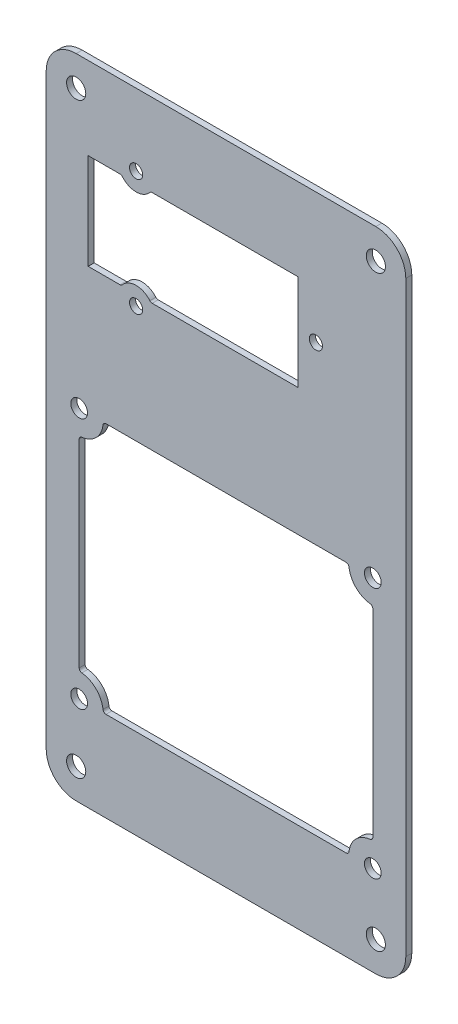
SolidWorks part; units mm, degrees
ref_plane "正面" through (0, 0, 0) normal (0, 0, 1) x (1, 0, 0)
ref_plane "平面" through (0, 0, 0) normal (0, 1, 0) x (1, 0, 0)
ref_plane "右側面" through (0, 0, 0) normal (1, 0, 0) x (0, 0, -1)
sketch "ｽｹｯﾁ1" plane through (0, 0, 0) normal (0, 0, 1) x (1, 0, 0)
  line L1 (-30, 54) -> (30, 54)
  line L2 (-30, 54) -> (-30, -54)
  line L3 (-30, -54) -> (30, -54)
  line L4 (30, 54) -> (30, -54)
  line L5 (-30, 54) -> (30, -54) construction
  line L6 (-30, -54) -> (30, 54) construction
  point P0 (0, 0)
  dimension "D1" = 60
  dimension "D2" = 108
extrude "ﾎﾞｽ - 押し出し1" add sketch "ｽｹｯﾁ1" along normal blind 1
sketch "ｽｹｯﾁ4" plane through (0, 0, 1) normal (0, 0, 1) x (1, 0, 0)
  line L0 (-30, -54) -> (30, -54) construction
  line L1 (-24.5, 3) -> (24.5, 3) construction
  line L2 (-24.5, 3) -> (-24.5, -39) construction
  line L3 (-24.5, -39) -> (24.5, -39) construction
  line L4 (24.5, 3) -> (24.5, -39) construction
  circle A0 centre (-24.5, 3) radius 1.4
  circle A1 centre (-24.5, -39) radius 1.4
  circle A2 centre (24.5, 3) radius 1.4
  circle A3 centre (24.5, -39) radius 1.4
  point P4 (0, -39)
  point P7 (0, -54)
  dimension "D5" = 2.8
  dimension "D6" = 2.8
  dimension "D7" = 2.8
  dimension "D8" = 2.8
  dimension "D1" = 49
  dimension "D2" = 42
  dimension "D3" = 0
  dimension "D4" = 15
extrude "ｶｯﾄ - 押し出し2" cut sketch "ｽｹｯﾁ4" against normal blind 10
sketch "ｽｹｯﾁ9" plane through (0, 0, 1) normal (0, 0, 1) x (1, 0, 0)
  line L0 (30, -54) -> (30, 54) construction
  line L1 (-25, -49) -> (25, -49) construction
  line L2 (-25, -49) -> (-25, 49) construction
  line L3 (-25, 49) -> (25, 49) construction
  line L4 (25, -49) -> (25, 49) construction
  line L5 (-25, -49) -> (25, 49) construction
  line L6 (-25, 49) -> (25, -49) construction
  line L8 (30, 54) -> (-30, 54) construction
  circle A0 centre (25, 49) radius 1.6
  circle A1 centre (-25, 49) radius 1.6
  circle A2 centre (-25, -49) radius 1.6
  circle A3 centre (25, -49) radius 1.6
  point P0 (0, 0)
  dimension "D3" = 3.2
  dimension "D4" = 3.2
  dimension "D5" = 3.2
  dimension "D6" = 3.2
  dimension "D1" = 5
  dimension "D2" = 5
extrude "ｶｯﾄ - 押し出し5" cut sketch "ｽｹｯﾁ9" against normal through all
fillet "ﾌｨﾚｯﾄ1" radius 5 4 edges at (-30, -54, 0.5) (30, -54, 0.5) (-30, 54, 0.5) (30, 54, 0.5)
sketch "ｽｹｯﾁ10" plane through (0, 0, 1) normal (0, 0, 1) x (1, 0, 0)
  line L0 (-15, 22.5) -> (-15, 42) construction
  line L1 (-30, 49) -> (-30, -49) construction
  line L2 (25, 54) -> (-25, 54) construction
  line L4 (-15, 22.5) -> (15, 22.5) construction
  line L5 (-15, 22.5) -> (-15, 42) construction
  line L6 (-15, 42) -> (15, 42) construction
  line L7 (15, 22.5) -> (15, 42) construction
  circle A0 centre (-15, 22.5) radius 1.1
  circle A1 centre (-15, 42) radius 1.1
  circle A2 centre (15, 32.25) radius 1.1
  dimension "D4" = 2.2
  dimension "D5" = 2.2
  dimension "D7" = 2.2
  dimension "D1" = 19.5
  dimension "D2" = 15
  dimension "D3" = 12
  dimension "D6" = 30
extrude "ｶｯﾄ - 押し出し6" cut sketch "ｽｹｯﾁ10" against normal blind 10
sketch "ｽｹｯﾁ12" plane through (0, 0, 1) normal (0, 0, 1) x (1, 0, 0)
  line L1 (-24.5, -39) -> (24.5, -39)
  line L2 (-24.5, -39) -> (-24.5, 3)
  line L3 (-24.5, 3) -> (24.5, 3)
  line L4 (24.5, -39) -> (24.5, 3)
  circle A0 centre (-24.5, -39) radius 4
  circle A1 centre (-24.5, 3) radius 4
  circle A2 centre (24.5, -39) radius 4
  circle A3 centre (24.5, 3) radius 4
  dimension "D1" = 8
  dimension "D2" = 8
  dimension "D3" = 8
  dimension "D4" = 8
extrude "ｶｯﾄ - 押し出し7" cut sketch "ｽｹｯﾁ12" against normal blind 10 contours A3 L3 A1 L2 A0 L1 A2 L4 region at (0, -18, 1)
sketch "ｽｹｯﾁ13" plane through (0, 0, 1) normal (0, 0, 1) x (1, 0, 0)
  line L1 (-23, 24.25) -> (12, 24.25)
  line L2 (-23, 24.25) -> (-23, 40.25)
  line L3 (-23, 40.25) -> (12, 40.25)
  line L4 (12, 24.25) -> (12, 40.25)
  circle A0 centre (-15, 22.5) radius 1.1 construction
  circle A1 centre (15, 32.25) radius 1.1 construction
  circle A2 centre (-15, 22.5) radius 3
  circle A3 centre (-15, 42) radius 3
  point P6 (12, 32.25)
  dimension "D5" = 6
  dimension "D6" = 6
  dimension "D1" = 35
  dimension "D2" = 16
  dimension "D3" = 8
  dimension "D4" = 0
extrude "ｶｯﾄ - 押し出し8" cut sketch "ｽｹｯﾁ13" against normal blind 10 contours A3 L3 L2 L1 A2 L4 region at (-5.353, 32.25, 1)
fillet "ﾌｨﾚｯﾄ2" radius 0.5 8 edges at (20.5, -39, 0.5) (24.5, -35, 0.5) (24.5, -1, 0.5) (20.5, 3, 0.5) (-20.5, 3, 0.5) (-24.5, -1, 0.5) (-20.5, -39, 0.5) (-24.5, -35, 0.5)
fillet "ﾌｨﾚｯﾄ3" radius 0.5 4 edges at (-12.5633, 24.25, 0.5) (-17.4367, 24.25, 0.5) (-17.4367, 40.25, 0.5) (-12.5633, 40.25, 0.5)
